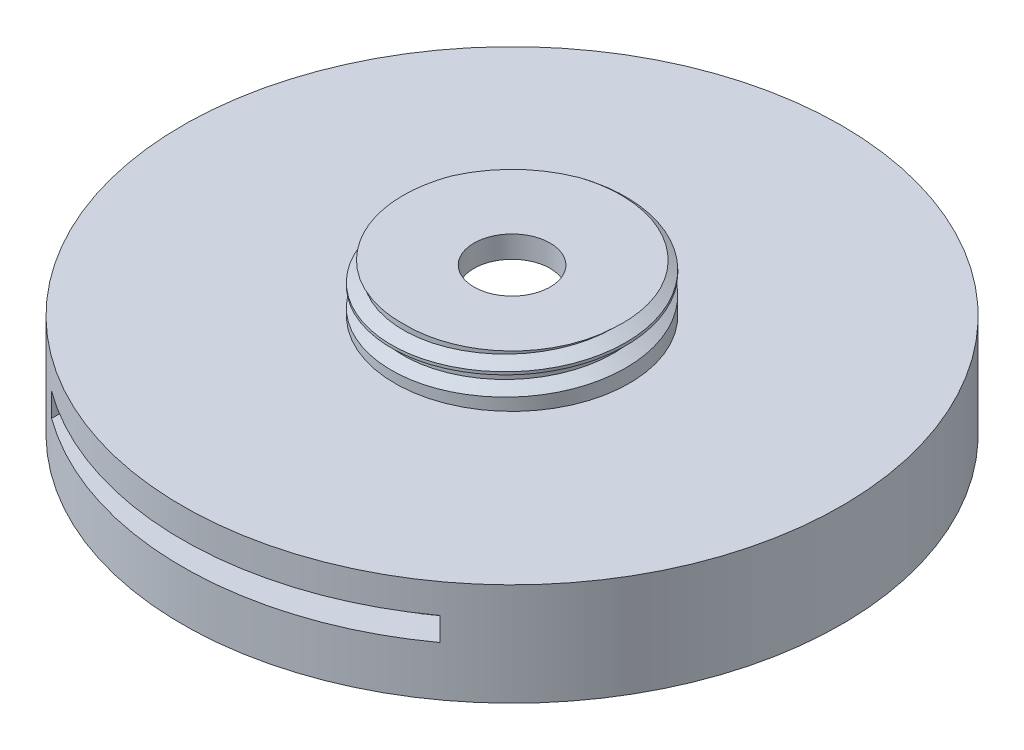
SolidWorks part; units mm, degrees
ref_plane "Ebene vorne" through (0, 0, 0) normal (0, 0, 1) x (1, 0, 0)
ref_plane "Ebene oben" through (0, 0, 0) normal (0, 1, 0) x (1, 0, 0)
ref_plane "Ebene rechts" through (0, 0, 0) normal (1, 0, 0) x (0, 0, -1)
sketch "Skizze1" plane through (0, 0, 0) normal (0, 1, 0) x (1, 0, 0)
  circle A0 centre (-18.0437, 0) radius 5
extrude "Zylinder" add sketch "Skizze1" along normal blind 2.2
ref_plane "Ebene auf Zylinder" through (0, 2.2, 0) normal (0, 1, 0) x (1, 0, 0)
sketch "Skizze4" plane through (0, 2.2, 0) normal (0, 1, 0) x (1, 0, 0)
  circle A0 centre (-18.0437, 0) radius 4.5
extrude "Schnitt-Linear austragen1" cut sketch "Skizze4" against normal blind 5 and the other way blind 10
ref_plane "Eben im Zylinder" through (0, 0.8, 0) normal (0, 1, 0) x (1, 0, 0)
sketch "Skizze5" plane through (0, 0.8, 0) normal (0, 1, 0) x (1, 0, 0)
  circle A0 centre (-18.0437, 0) radius 4.55
ref_plane "Ebene für Aufsatz" through (0, 0, 0) normal (0, -1, 0) x (-1, 0, 0)
sketch "Skizze6" plane through (0, 0, 0) normal (0, -1, 0) x (-1, 0, 0)
  circle A0 centre (18.0437, 0) radius 22.5
extrude "Fassung Objektträgergewinde" add sketch "Skizze6" along normal blind 7
ref_plane "Ebene auf Objektträgerfassung" through (0, -7, 0) normal (0, -1, 0) x (-1, 0, 0)
sketch "Skizze11" plane through (0, -7, 0) normal (0, -1, 0) x (-1, 0, 0)
  circle A0 centre (18.0437, 0) radius 20.3
extrude "Bohrung für Innengewinde" cut sketch "Skizze11" against normal blind 6
sketch "Skizze12" plane through (0, 0, 0) normal (0, -1, 0) x (-1, 0, 0)
  circle A2 centre (18.0437, 0) radius 4.5
ref_plane "Ebene1" through (0, 0, 0) normal (0, -1, 0) x (-1, 0, 0)
sketch "Skizze13" plane through (0, 0, 0) normal (0, -1, 0) x (-1, 0, 0)
  circle A0 centre (18.0437, 0) radius 8
  dimension "D1" = 16
extrude "Zylinder für Gewinde" add sketch "Skizze13" against normal blind 3
ref_plane "Ebene4" through (0, -1, 0) normal (0, -1, 0) x (-1, 0, 0)
sketch "Skizze15" plane through (0, -1, 0) normal (0, -1, 0) x (-1, 0, 0)
  circle A0 centre (18.0437, 0) radius 9.2938
sketch "Skizze16" plane through (0, -7, 0) normal (0, -1, 0) x (-1, 0, 0)
  circle A0 centre (18.0437, 0) radius 2.6
  dimension "D1" = 5.2
extrude "Linseneinsatz" cut sketch "Skizze16" against normal blind 10
thread "Gewinde1" pitch 1.5 method cut profile "Gewindeprofil1" start angle 0, offset 1.6, length 3.5, pitch 1.5, diameter 16
ref_plane "Ebene6" through (-26.0437, 4.6, 0) normal (0, 0, 1) x (-1, 0, 0)
sketch "Gewindeprofil1" plane through (-26.0437, 4.6, 0) normal (0, 0, 1) x (-1, 0, 0)
  line L0 (0, 0) -> (0, 1.5) construction
  line L11 (0, 0) -> (0, 1.3125)
  line L12 (0, 1.3125) -> (-0.8119, 0.8437)
  line L13 (-0.8119, 0.8437) -> (-0.8119, 0.4687)
  line L15 (-0.8119, 0.4687) -> (0, 0)
  line L17 (-0.8119, 0.6562) -> (0, 0.6562) construction
  point P2 (0, 0)
  dimension "Pitch" = 1.5
  dimension "Profile_Angle" = 60
  dimension "Profile_Land" = 0.375
  dimension "Profile_Height" = 0.8119
ref_plane "Ebene7" through (0, -2, 0) normal (0, 1, 0) x (1, 0, 0)
sketch "Skizze17" plane through (0, -2, 0) normal (0, 1, 0) x (1, 0, 0)
  line L1 (-4.7937, -24.7706) -> (-31.2937, -24.7706)
  line L2 (-4.7937, -24.7706) -> (-4.7937, 24.7706)
  line L3 (-4.7937, 24.7706) -> (-31.2937, 24.7706)
  line L4 (-31.2937, -24.7706) -> (-31.2937, 24.7706)
  line L5 (-4.7937, -24.7706) -> (-31.2937, 24.7706) construction
  line L6 (-4.7937, 24.7706) -> (-31.2937, -24.7706) construction
  point P0 (-18.0437, 0)
  dimension "D1" = 26.5
extrude "Schlitz für Slide" cut sketch "Skizze17" against normal blind 1.6
sketch "Skizze21" plane through (0, -1, 0) normal (0, -1, 0) x (-1, 0, 0)
  circle A0 centre (18.0437, 0) radius 6.5
  dimension "D1" = 13
extrude "Filtereinsatz" cut sketch "Skizze21" against normal blind 2.5
ref_plane "Ebene für Schrift" through (0, 0, 0) normal (0, 1, 0) x (1, 0, 0)
sketch "Skizze18" plane through (0, 0, 0) normal (0, 1, 0) x (1, 0, 0)
  text T0 "\r\n\r\n5mm" font "Century Gothic" height 3.5
